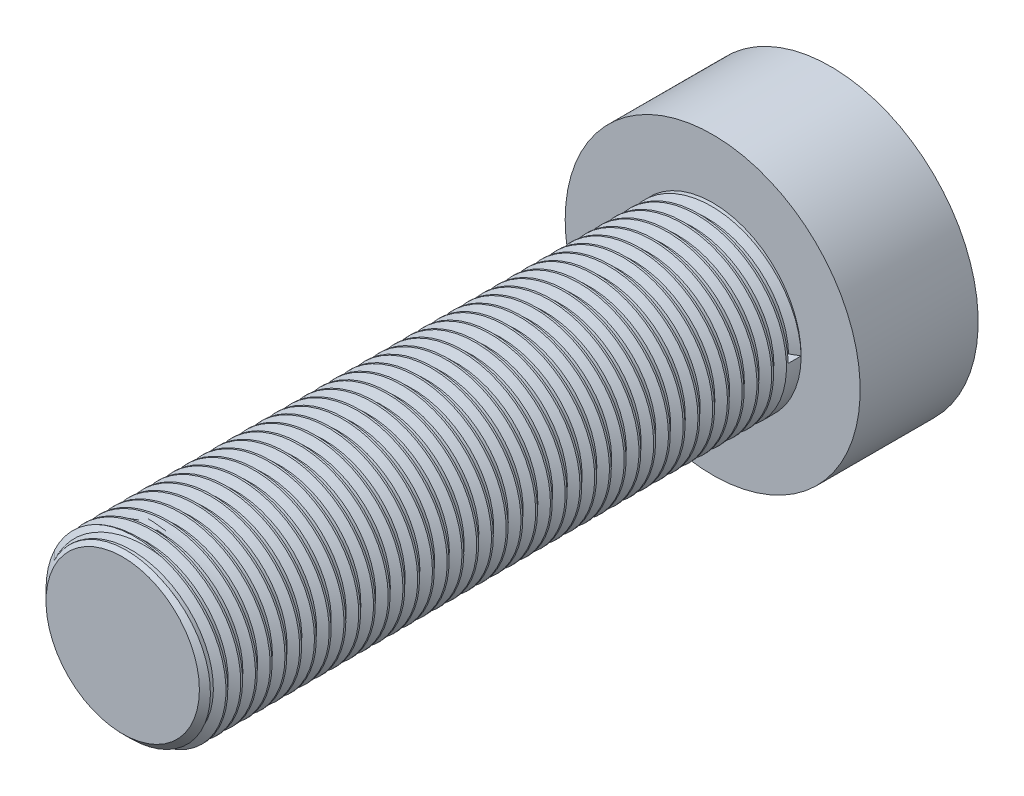
SolidWorks part; units mm, degrees
ref_plane "Front Plane" through (0, 0, 0) normal (0, 0, 1) x (1, 0, 0)
ref_plane "Top Plane" through (0, 0, 0) normal (0, 1, 0) x (1, 0, 0)
ref_plane "Right Plane" through (0, 0, 0) normal (1, 0, 0) x (0, 0, -1)
sketch "Sketch1" plane through (0, 0, 0) normal (0, 0, 1) x (1, 0, 0)
  circle A0 centre (0, 0) radius 1.5
  dimension "D1" = 3
extrude "Boss-Extrude1" add sketch "Sketch1" along normal blind 10
sketch "Sketch2" plane through (0, 0, 0) normal (0, 0, -1) x (-1, 0, 0)
  circle A0 centre (0, 0) radius 2.5
  dimension "D1" = 5
extrude "Boss-Extrude2" add sketch "Sketch2" along normal blind 2
chamfer "Chamfer1" distance 0.2 angle 45 1 edges at (1.5, 0, 10)
thread "Thread3" pitch 0.25 method cut profile "Thread Profile4" start angle 0, offset 0, length 10, pitch 0.25, diameter 3
ref_plane "Plane4" through (1.5, 0, 0) normal (0, -1, 0) x (1, 0, 0)
sketch "Thread Profile4" plane through (1.5, 0, 0) normal (0, -1, 0) x (1, 0, 0)
  line L0 (0, 0) -> (0, 0.25) construction
  line L11 (0, 0) -> (0, 0.2187)
  line L12 (0, 0.2187) -> (-0.1353, 0.1406)
  line L13 (-0.1353, 0.1406) -> (-0.1353, 0.0781)
  line L15 (-0.1353, 0.0781) -> (0, 0)
  line L17 (-0.1353, 0.1094) -> (0, 0.1094) construction
  point P2 (0, 0)
  dimension "Pitch" = 0.25
  dimension "Profile_Angle" = 60
  dimension "Profile_Land" = 0.0625
  dimension "Profile_Height" = 0.1353
